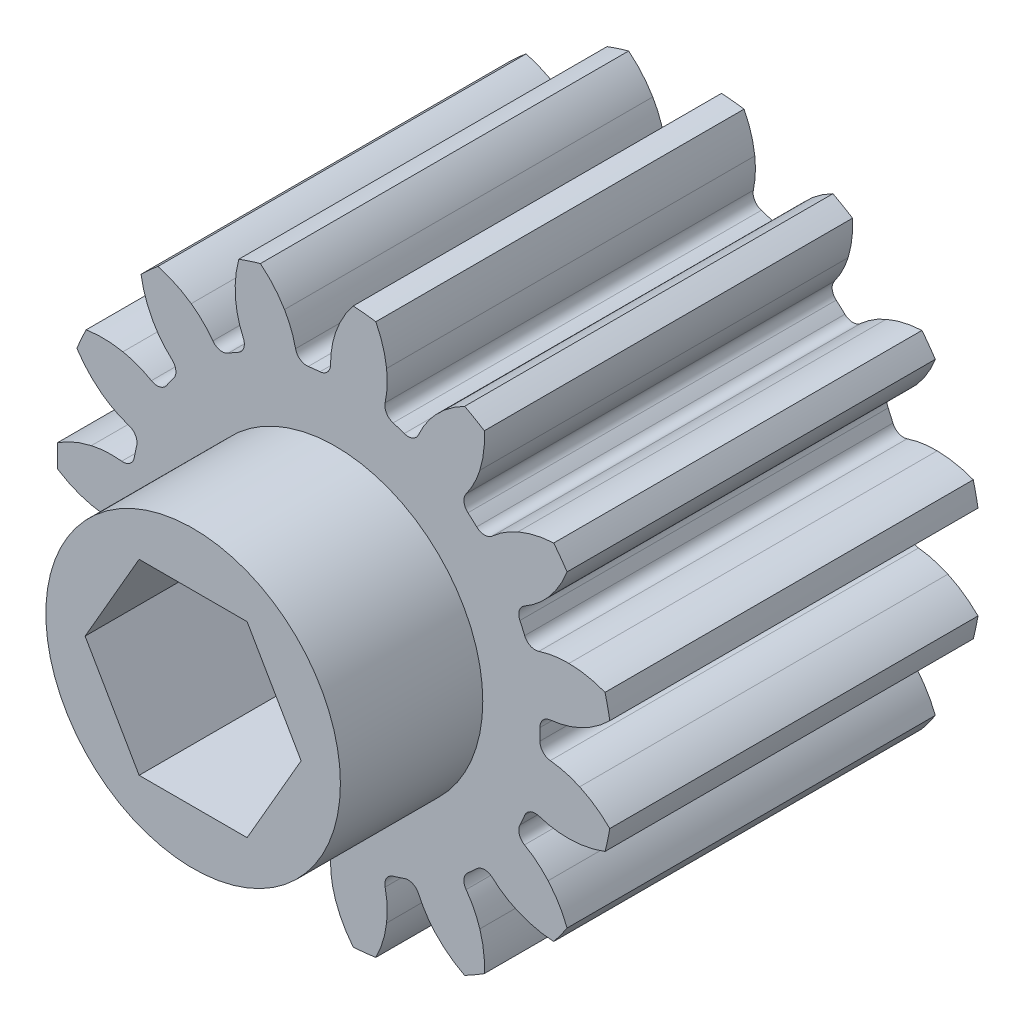
SolidWorks part; units mm, degrees
other "DetailItem7"
other "DetailItem8"
material "Markforged"
ref_plane "Front" through (0, 0, 0) normal (0, 0, 1) x (1, 0, 0)
ref_plane "Top" through (0, 0, 0) normal (0, 1, 0) x (1, 0, 0)
ref_plane "Right" through (0, 0, 0) normal (1, 0, 0) x (0, 0, -1)
sketch "Sketch1" plane through (0, 0, 0) normal (0, 0, 1) x (1, 0, 0)
  line L0 (0, 0) -> (6.35, 0) construction
  line L1 (6.35, 0) -> (7.1967, 0) construction
  circle A0 centre (0, 0) radius 6.35 construction
  circle A1 centre (0, 0) radius 7.1967
  dimension "D1" = 12.7
  dimension "D2" = 0.8467
extrude "Round Stock" add sketch "Sketch1" along normal mid plane 9.525
sketch "Sketch2" plane through (0, 0, 4.7625) normal (0, 0, 1) x (1, 0, 0)
  line L0 (0, 0) -> (5.2917, 0) construction
  line L1 (5.2917, 0) -> (6.35, 0) construction
  line L2 (0, 0) -> (-7.1967, 0) construction
  line L3 (0, 0) -> (-6.5745, -2.9271) construction
  line L4 (-6.6884, -2.6565) -> (-6.0396, -1.961) construction
  line L5 (-6.0396, -1.961) -> (-5.0824, -1.4735) construction
  line L6 (-7.1907, -0.2936) -> (-6.3151, -0.6651) construction
  line L7 (-6.3151, -0.6651) -> (-5.2423, -0.7211) construction
  line L8 (-5.7691, -2.5686) -> (-6.0396, -1.961) construction
  line L9 (-6.3151, -0.6651) -> (-6.3151, 0) construction
  line L12 (0, 0) -> (-6.3151, -0.6651) construction
  line L13 (0, 0) -> (-6.0396, -1.961) construction
  line L14 (-6.0396, -1.961) -> (-4.9937, -5.1821) construction
  line L15 (-6.3151, -0.6651) -> (-6.6698, 2.703) construction
  line L16 (-6.0396, -1.961) -> (-6.3151, -0.6651) construction
  line L17 (-5.176, -1.1002) -> (-5.2423, -0.7211) construction
  line L18 (-5.176, -1.1002) -> (-5.0824, -1.4735) construction
  circle A0 centre (0, 0) radius 6.35 construction
  circle A1 centre (0, 0) radius 5.2917 construction
  circle A2 centre (0, 0) radius 7.1967 construction
  arc A3 (-6.6884, -2.6565) -> (-7.1907, -0.2936) centre (0, 0) cw
  arc A4 (-5.0824, -1.4735) -> (-5.2423, -0.7211) centre (0, 0) cw construction
  arc A6 (-6.6884, -2.6565) -> (-6.0396, -1.961) centre (-4.4502, -4.0942) cw
  arc A7 (-7.1907, -0.2936) -> (-6.3151, -0.6651) centre (-5.7307, 1.9302) ccw
  arc A8 (-6.0396, -1.961) -> (-5.3395, -1.6003) centre (-4.6032, -3.8888) cw
  arc A9 (-6.3151, -0.6651) -> (-5.5288, -0.7099) centre (-5.787, 1.6803) ccw
  arc A10 (-5.3395, -1.6003) -> (-5.1423, -1.2483) centre (-5.4303, -1.3182) ccw
  arc A11 (-5.5288, -0.7099) -> (-5.2055, -0.9512) centre (-5.497, -1.0045) cw
  arc A12 (-5.1423, -1.2483) -> (-5.2055, -0.9512) centre (0, 0) cw
  dimension "D6" = 12.7
  dimension "D9" = 0.2963
  dimension "D12" = 2.6602
  dimension "D2" = 1.0583
  dimension "D3" = 24
  dimension "D4" = 0.6651
  dimension "D5" = 0.6651
  dimension "D11" = 1.3249
  dimension "D8" = 20
  dimension "D7" = 20
  dimension "D14" = 9
  dimension "D15" = 9
extrude "Single Tooth" cut sketch "Sketch2" against normal through all
ref_axis "Axis" through (0, 0, 50) along (0, 0, -1)
pattern_circular "Tooth Pattern" count 15 over 360 about axis through (0, 0, 50) along (0, 0, -1) of "Single Tooth"
sketch "Sketch4" plane through (0, 0, 4.7625) normal (0, 0, 1) x (1, 0, 0)
  circle A0 centre (0, 0) radius 3.81
  dimension "D1" = 7.62
extrude "TopBearingBoss" add sketch "Sketch4" along normal blind 3.683
mirror "BottomBearingBoss" [suppressed] about plane through (0, 0, 0) normal (0, 0, 1)
sketch "Sketch5" plane through (0, 0, 0) normal (0, 0, 1) x (1, 0, 0)
  circle A0 centre (0, 0) radius 2.4193
  dimension "D1" = 4.8387
extrude "RoundBore" cut sketch "Sketch5" against normal through all both and the other way through all
sketch "Sketch6" plane through (0, 0, 0) normal (0, 0, 1) x (1, 0, 0)
  line L1 (1.3968, 2.4194) -> (-1.3968, 2.4193)
  line L2 (-1.3968, 2.4193) -> (-2.7936, 0)
  line L3 (-2.7936, 0) -> (-1.3968, -2.4194)
  line L4 (-1.3968, -2.4194) -> (1.3968, -2.4194)
  line L5 (1.3968, -2.4194) -> (2.7936, 0)
  line L6 (2.7936, 0) -> (1.3968, 2.4194)
  circle A0 centre (0, 0) radius 2.4193 construction
  circle A1 centre (0, 0) radius 2.4193 construction
extrude "Hex" cut sketch "Sketch6" against normal through all both and the other way through all
sketch "Sketch7" plane through (0, 0, 4.7625) normal (0, 0, 1) x (1, 0, 0)
  line L0 (-10.955, 3.3496) -> (10.955, 3.3496) construction
  line L1 (0, 0) -> (0, 3.3496) construction
  text T0 "15" font "Adobe Gothic Std B" height 3.5
  dimension "D1" = 3.3496
extrude "ToothCount" [suppressed] cut sketch "Sketch7" against normal blind 0.762
equation "\"N_teeth\"= \"No_Teeth\""
equation "\"pitch_diameter\"= \"N_teeth\" / \"Pitch\""
equation "\"Pd\"=\"N_teeth\"/\"pitch_diameter\""
equation "\"addendum\"=1.000/\"Pd\""
equation "\"face_width\"=0.375000"
equation "\"deddendum\"=1.250/\"Pd\""
equation "\"D3@Sketch2\" = 360/\"N_teeth\""
equation "\"tooth_thickness\"=1.571/\"Pd\""
equation "\"D4@Sketch2\" = \"tooth_thickness\"/2"
equation "\"D5@Sketch2\" = \"tooth_thickness\"/2"
equation "\"Pressure_Angle\"= iif ( \"Pitch\" = 20 , 14.500000 , iif ( \"Pitch\" = 32 , 20 , 20 ) )"
equation "\"base_fillet\"=0.35/\"Pd\""
equation "\"D12@Sketch2\" = 2*\"tooth_thickness\""
equation "\"hub_projection\"=0.250000"
equation "\"sss_diam\"= 0.062500"
equation "\"D1@Sketch1\"=\"pitch_diameter\""
equation "\"D2@Sketch1\"=\"addendum\""
equation "\"D1@Round Stock\" = \"face_width\""
equation "\"D2@Sketch2\"=\"deddendum\""
equation "\"D6@Sketch2\"=\"pitch_diameter\""
equation "\"D7@Sketch2\"=\"Pressure_Angle\""
equation "\"D8@Sketch2\"=\"D7@Sketch2\""
equation "\"D9@Sketch2\"=\"base_fillet\""
equation "\"D1@Tooth Pattern\" = \"N_teeth\""
equation "\"Pitch\"= \"GearPitch\""
equation "\"BossDia\"= \"BoreDia\" * 1.3"
equation "\"D1@Sketch5\"=\"BoreDia\"+\"PrintTol\""
equation "\"Hex\"= iif ( \"HexBore\" = 1 , \"unsuppressed\" , \"suppressed\" )"
equation "\"TopBearingBoss\" = iif ( \"Bearing_Boss\" = 0 , \"suppressed\" , \"unsuppressed\" )"
equation "\"BottomBearingBoss\"= iif ( \"Bearing_Boss\" > 1 , \"unsuppressed\" , \"suppressed\" )"
equation "\"D1@Sketch7\"=\"BossDia\"/2+.01"
equation "\"ToothCount\"= iif ( \"No_Teeth\" < 22 , \"suppressed\" , \"unsuppressed\" )"
